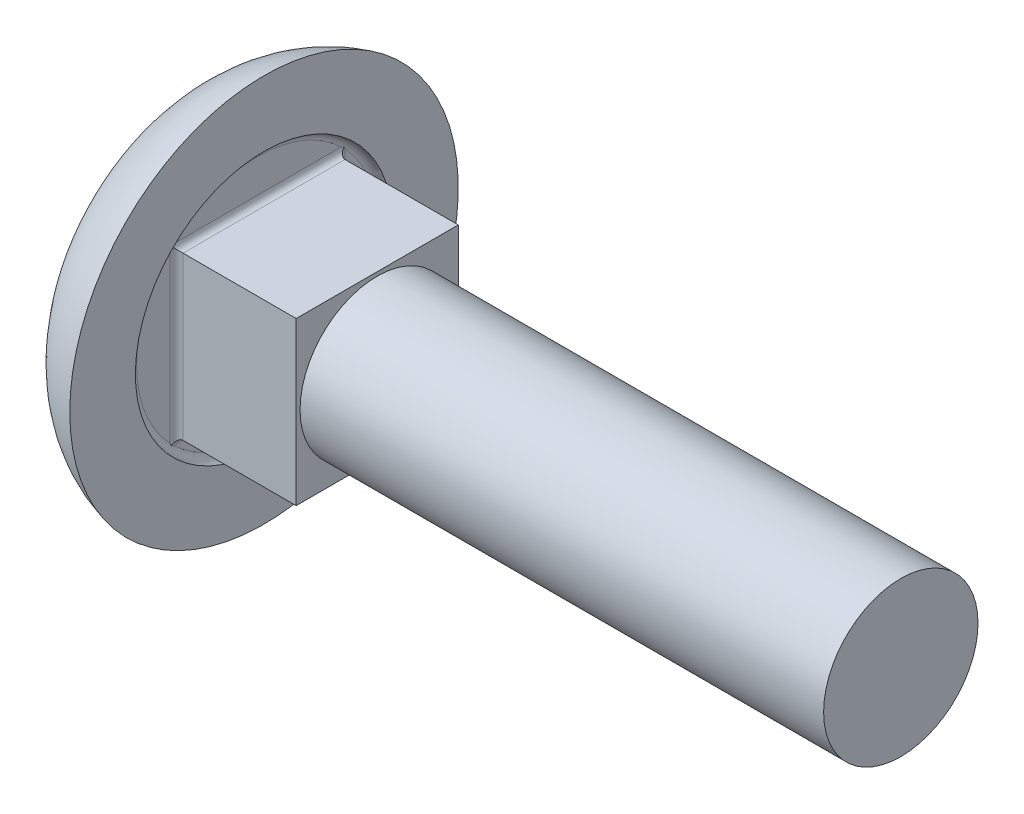
SolidWorks part; units mm, degrees
ref_plane "Front" through (0, 0, 0) normal (0, 0, 1) x (1, 0, 0)
ref_plane "Top" through (0, 0, 0) normal (0, 1, 0) x (1, 0, 0)
ref_plane "Right" through (0, 0, 0) normal (1, 0, 0) x (0, 0, -1)
sketch "Sketch1" plane through (0, 0, 0) normal (0, 0, 1) x (1, 0, 0)
  line L0 (-17.7731, 0) -> (33.4439, 0) construction
  line L1 (3.98, 7.55) -> (3.98, 0)
  line L2 (3.98, 0) -> (0, 0)
  arc A0 (0, 0) -> (0.8068, 4.684) centre (14, 0) cw
  arc A1 (0.8068, 4.684) -> (3.98, 7.55) centre (5.0475, 3.1784) cw
  dimension "R1" = 4.5
  dimension "r" = 14
  dimension "k" = 3.98
  dimension "dk" = 15.1
revolve "BaseHead" add sketch "Sketch1" angle 360 about L0
sketch "Sketch2" plane through (3.98, 0, 0) normal (1, 0, 0) x (0, 0, -1)
  circle A0 centre (0, 0) radius 5
  dimension "d1" = 10
extrude "Cut-Extrude1" cut sketch "Sketch2" against normal blind 0.25
ref_plane "Plan1" through (8.38, 0, 0) normal (1, 0, 0) x (0, 0, -1)
sketch "Sketch3" plane through (8.38, 0, 0) normal (1, 0, 0) x (0, 0, -1)
  line L1 (3.15, -3.15) -> (3.15, 3.15)
  line L2 (3.15, 3.15) -> (-3.15, 3.15)
  line L3 (-3.15, 3.15) -> (-3.15, -3.15)
  line L4 (-3.15, -3.15) -> (3.15, -3.15)
  circle A0 centre (0, 0) radius 3.15 construction
  dimension "Ss" = 6.3
extrude "Neck" add sketch "Sketch3" against normal up to next
fillet "Fillet" radius 0.25 4 edges at (3.73, -3.15, 0) (3.73, 0, 3.15) (3.73, 3.15, 0) (3.73, 0, -3.15)
sketch "Sketch4" plane through (3.73, 0, 0) normal (1, 0, 0) x (0, 0, -1)
  circle A0 centre (0, 0) radius 3
extrude "BaseBody" add sketch "Sketch4" along normal blind 25
cosmetic thread "ThreadCosmetic1" [suppressed] parameters "b"=18, "D2"=4.917
fillet "HeadFillet" radius 0.3 1 edges at (3.73, 0, -5)
sketch "Sketch5" plane through (0, 0, 0) normal (0, 0, 1) x (1, 0, 0)
  line L0 (28.4592, 3.2) -> (29.0008, 3.2)
  line L1 (29.0008, 3.2) -> (29.0008, 3)
  line L2 (29.0008, 3) -> (28.73, 2.531)
  line L3 (28.4592, 3) -> (28.73, 2.531)
  line L4 (28.4592, 3.2) -> (28.4592, 3)
  line L5 (28.73, 0) -> (0, 0) construction
  line L6 (28.4592, 3) -> (29.0008, 3) construction
  line L7 (28.73, 3) -> (28.73, 2.531) construction
  line L8 (28.73, 3) -> (8.38, 3) construction
  line L9 (28.73, -3) -> (28.73, 3) construction
  point P5 (28.73, 3.2)
revolve "Cut-Revolve10" [suppressed] cut sketch "Sketch5" angle 360 about L5
pattern_linear "LPattern10" [suppressed] count 28 spacing 0.6498 of bodies 105
equation "\"D2@Sketch5\" = (  \"d@Sketch4\" - \"D2@ThreadCosmetic1\" )  / 2"
equation "\"D3@LPattern10\" = \"D2@Sketch5\" * 1.2"
equation "\"D1@LPattern10\" = \"b@ThreadCosmetic1\" / \"D3@LPattern10\""
